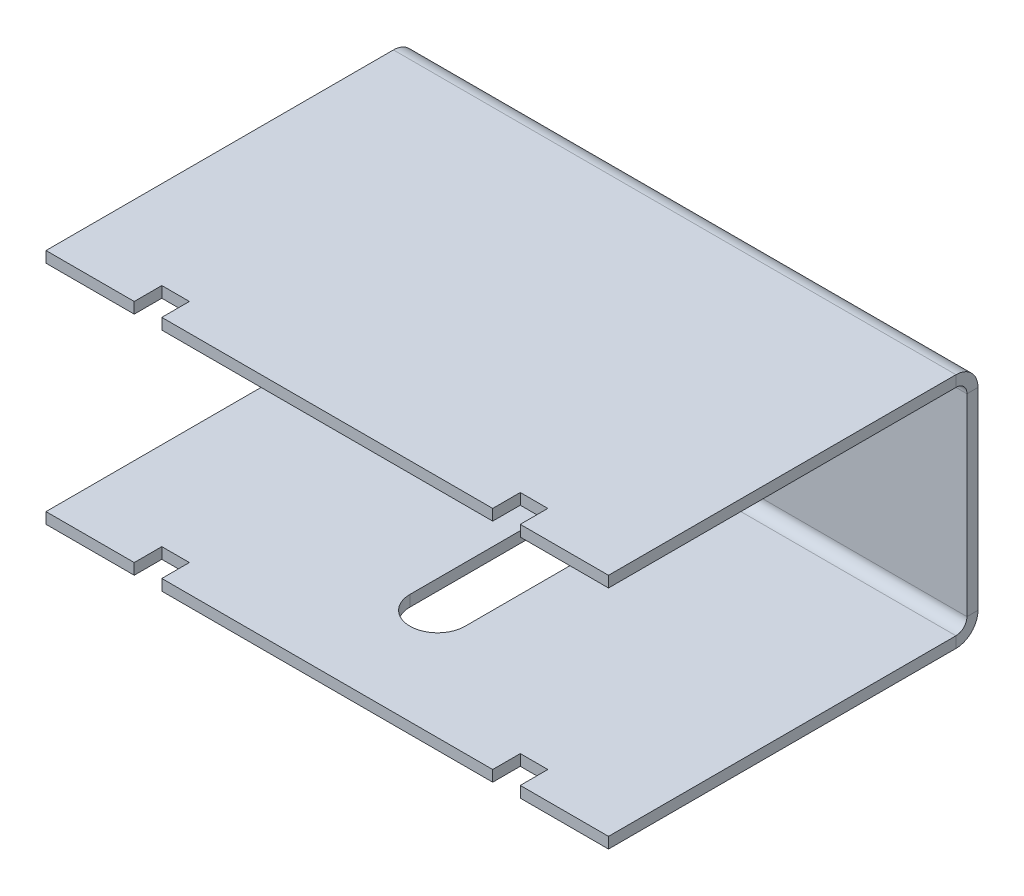
SolidWorks part; units mm, degrees
note: The reader was unsure of these and kept them because the rebuilt part matched: bend radius of "基体-法兰1", "基体折弯1", "基体折弯2".
material "锻制不锈钢"
ref_plane "前视基准面" through (0, 0, 0) normal (0, 0, 1) x (1, 0, 0)
ref_plane "上视基准面" through (0, 0, 0) normal (0, 1, 0) x (1, 0, 0)
ref_plane "右视基准面" through (0, 0, 0) normal (1, 0, 0) x (0, 0, -1)
sketch "草图1" plane through (0, 0, 0) normal (1, 0, 0) x (0, 0, -1)
  line L1 (-32.5, -19.5) -> (32.5, -19.5)
  line L2 (-32.5, -19.5) -> (-32.5, 19.5) construction
  line L3 (-32.5, 19.5) -> (32.5, 19.5)
  line L4 (32.5, -19.5) -> (32.5, 19.5)
  line L5 (-32.5, -19.5) -> (32.5, 19.5) construction
  line L6 (-32.5, 19.5) -> (32.5, -19.5) construction
  point P0 (0, 0)
  dimension "D1" = 65
  dimension "D2" = 39
base flange "基体-法兰1" sketch "草图1" end condition mid plane depth 102 reverse direction no thickness 2 reverse thickness direction yes bend radius 2
bend "基体折弯1" bend radius 2 bend angle 90 parameters "D5"=1
bend "基体折弯2" bend radius 2 bend angle 90 parameters "D5"=2
sketch "草图2" plane through (0, -21.5, 0) normal (0, -1, 0) x (1, 0, 0)
  line L0 (0, 12.5) -> (0, -14.5) construction
  line L1 (5, 12.5) -> (5, -14.5)
  line L2 (-5, 12.5) -> (-5, -14.5)
  line L5 (51, 32.5) -> (-51, 32.5) construction
  line L6 (51, -34.5) -> (-51, -34.5) construction
  arc A0 (5, 12.5) -> (-5, 12.5) centre (0, 12.5) ccw
  arc A1 (-5, -14.5) -> (5, -14.5) centre (0, -14.5) ccw
  point P2 (0, -1)
  dimension "D1" = 10
  dimension "D3" = 15
  dimension "D2" = 15
extrude "切除-拉伸1" cut sketch "草图2" against normal up to next normal cut yes
sketch "草图3" plane through (0, 21.5, 0) normal (0, 1, 0) x (1, 0, 0)
  line L0 (51, -32.5) -> (-51, -32.5) construction
  line L1 (-35, -37.5) -> (-30, -37.5)
  line L2 (-35, -37.5) -> (-35, -27.5)
  line L3 (-35, -27.5) -> (-30, -27.5)
  line L4 (-30, -37.5) -> (-30, -27.5)
  line L5 (-35, -37.5) -> (-30, -27.5) construction
  line L6 (-35, -27.5) -> (-30, -37.5) construction
  line L7 (0, 0) -> (0, -41.1927) construction
  line L8 (35, -27.5) -> (30, -37.5) construction
  line L9 (35, -37.5) -> (30, -27.5) construction
  line L10 (30, -37.5) -> (30, -27.5)
  line L11 (35, -27.5) -> (30, -27.5)
  line L12 (35, -37.5) -> (35, -27.5)
  line L13 (35, -37.5) -> (30, -37.5)
  point P0 (-32.5, -32.5)
  point P14 (32.5, -32.5)
  dimension "D1" = 5
  dimension "D2" = 5
  dimension "D3" = 60
extrude "切除-拉伸2" cut sketch "草图3" against normal through all normal cut yes
sketch "折弯-线1" [suppressed] plane through (0, 0, 0) normal (0, 1, 0) x (1, 0, 0)
sketch "边界框1" [suppressed] plane through (0, 0, 0) normal (0, 1, 0) x (1, 0, 0)
sheet metal parameters "钣金6" thickness 2 parameters "D1"=2
flat pattern "平板型式6" [suppressed]
sketch "折弯-线2" plane through (0, 0, 0) normal (0, 1, 0) x (1, 0, 0)
sketch "边界框2" [suppressed] plane through (0, 0, 0) normal (0, 1, 0) x (1, 0, 0)
bend of the flat pattern "展开-<基体折弯1>1"
bend of the flat pattern "展开-<基体折弯2>1"
sheet metal parameters "钣金7" thickness 2 parameters "D1"=2
flat pattern "平板型式6" [suppressed]
sketch "折弯-线2" plane through (0, 0, 0) normal (0, 1, 0) x (1, 0, 0)
sketch "边界框2" [suppressed] plane through (0, 0, 0) normal (0, 1, 0) x (1, 0, 0)
bend of the flat pattern "展开-<基体折弯1>1"
bend of the flat pattern "展开-<基体折弯2>1"
sheet metal parameters "钣金8" thickness 2 parameters "D1"=2
flat pattern "平板型式6"
sketch "折弯-线2" plane through (0, -21.5, 0) normal (0, -1, 0) x (-1, 0, 0)
  line L0 (-51, 32.8562) -> (51, 32.8562) construction
  line L1 (-51, 72.5686) -> (51, 72.5686) construction
  line L2 (-51, 32.8562) -> (51, 32.8562) construction
  line L3 (-51, 72.5686) -> (51, 72.5686) construction
sketch3d "边界框2" [suppressed]
  line L0 (102, 0, 0) -> (102, 170.4248, 0) construction
  line L1 (0, 0, 0) -> (0, 170.4248, 0) construction
  line L2 (102, 0, 0) -> (0, 0, 0) construction
  line L3 (102, 170.4248, 0) -> (0, 170.4248, 0) construction
bend of the flat pattern "展开-<基体折弯1>1"
bend of the flat pattern "展开-<基体折弯2>1"
